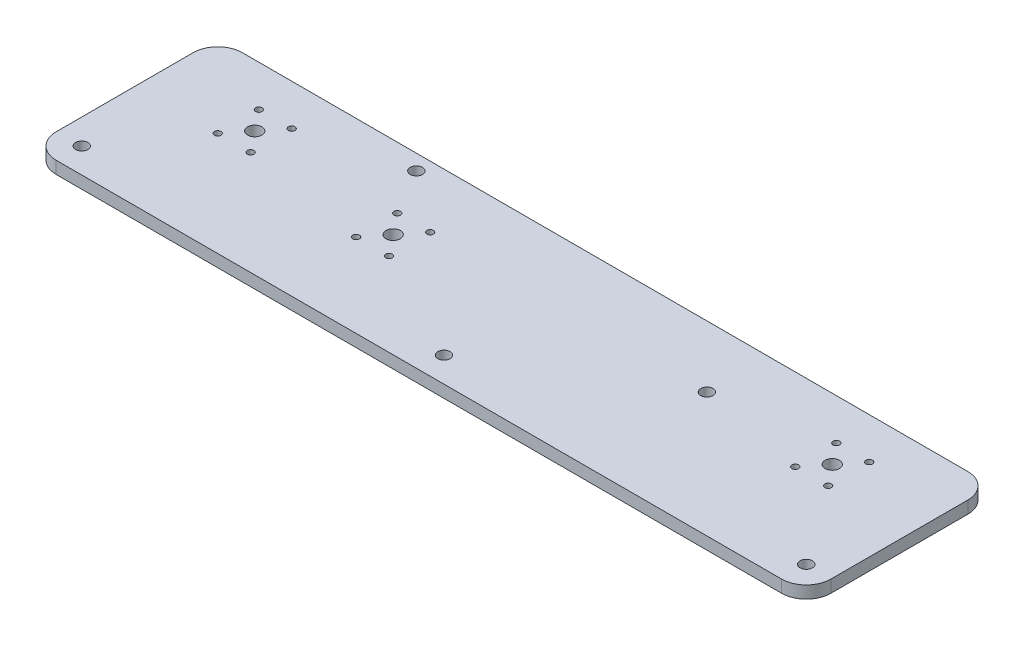
SolidWorks part; units mm, degrees
material "Policarbonato"
ref_plane "Plano frontal" through (0, 0, 0) normal (0, 0, 1) x (1, 0, 0)
ref_plane "Plano superior" through (0, 0, 0) normal (0, 1, 0) x (1, 0, 0)
ref_plane "Plano direito" through (0, 0, 0) normal (1, 0, 0) x (0, 0, -1)
sketch "Esboço1" plane through (0, 0, 0) normal (0, 1, 0) x (1, 0, 0)
  line L2 (-62.7345, -14) -> (-62.7345, 14) construction
  line L6 (188.965, -38.6487) -> (188.965, 28)
  line L7 (176.965, 40) -> (-176.0908, 40)
  line L8 (-188.0908, 28) -> (-188.0908, -38.6487)
  line L13 (-54.7345, -10) -> (-70.7345, -10) construction
  line L14 (-54.7345, -10) -> (-54.7345, 10) construction
  line L15 (-148.0908, 0) -> (-132.0908, 0) construction
  line L16 (-148.0908, 0) -> (-148.0908, 20) construction
  line L17 (-148.0908, 20) -> (-132.0908, 20) construction
  line L18 (-132.0908, 0) -> (-132.0908, 20) construction
  line L19 (-176.0908, -50.6487) -> (176.965, -50.6487)
  line L20 (-148.0908, 0) -> (-132.0908, 20) construction
  line L21 (-148.0908, 20) -> (-132.0908, 0) construction
  line L26 (-54.7345, 10) -> (-70.7345, 10) construction
  line L32 (-152.0908, 24) -> (-128.0908, -4) construction
  line L33 (-70.7345, -10) -> (-70.7345, 10) construction
  line L38 (-54.7345, -10) -> (-70.7345, 10) construction
  line L39 (-54.7345, 10) -> (-70.7345, -10) construction
  line L45 (148.965, 0) -> (132.965, 0) construction
  line L46 (148.965, 0) -> (148.965, 20) construction
  line L47 (148.965, 20) -> (132.965, 20) construction
  line L48 (132.965, 0) -> (132.965, 20) construction
  line L49 (148.965, 0) -> (132.965, 20) construction
  line L50 (148.965, 20) -> (132.965, 0) construction
  arc A0 (176.965, -50.6487) -> (188.965, -38.6487) centre (176.965, -38.6487) ccw
  arc A1 (188.965, 28) -> (176.965, 40) centre (176.965, 28) ccw
  arc A2 (-188.0908, 28) -> (-176.0908, 40) centre (-176.0908, 28) cw
  arc A3 (-188.0908, -38.6487) -> (-176.0908, -50.6487) centre (-176.0908, -38.6487) ccw
  circle A7 centre (-54.7345, -10) radius 1.6
  circle A8 centre (176.7481, -38.4318) radius 3
  circle A9 centre (0.4371, -38.4318) radius 3
  circle A10 centre (79.965, 10) radius 3
  circle A11 centre (-140.0908, 10) radius 3.5
  circle A13 centre (-148.0908, 0) radius 1.6
  circle A14 centre (-132.0908, 0) radius 1.6
  circle A15 centre (-132.0908, 20) radius 1.6
  circle A16 centre (-148.0908, 20) radius 1.6
  circle A22 centre (-83.9303, 32.5) radius 7.5 construction
  circle A24 centre (-83.9303, 32.5) radius 3
  circle A25 centre (-175.8739, -38.4318) radius 3
  circle A26 centre (-54.7345, 10) radius 1.6
  circle A27 centre (-70.7345, 10) radius 1.6
  circle A28 centre (-70.7345, -10) radius 1.6
  circle A29 centre (-62.7345, 0) radius 3.5
  circle A30 centre (132.965, 0) radius 1.6
  circle A31 centre (148.965, 0) radius 1.6
  circle A32 centre (148.965, 20) radius 1.6
  circle A33 centre (132.965, 20) radius 1.6
  circle A34 centre (140.965, 10) radius 3.5
  point P6 (-62.7345, 0)
  point P33 (0.4371, 40)
  point P39 (140.965, 10)
  dimension "D2" = 377.0558
  dimension "D4" = 7
  dimension "D6" = 12.2169
  dimension "D8" = 125.3563
  dimension "D10" = 48
  dimension "D12" = 16
  dimension "D15" = 20
  dimension "D17" = 6
  dimension "D1" = 12
  dimension "D7" = 16
  dimension "D9" = 30
  dimension "D11" = 20
  dimension "D16" = 3.2
  dimension "D20" = 48
  dimension "D25" = 56.1605
  dimension "D26" = 3.2
  dimension "D27" = 7
  dimension "D28" = 15
  dimension "D29" = 30
  dimension "D13" = 3.2
  dimension "D14" = 7
  dimension "D30" = 109
  dimension "D3" = 90.6487
  dimension "D5" = 12.2169
  dimension "D18" = 12.2169
  dimension "D19" = 50.6487
  dimension "D21" = 30
  dimension "D22" = 16
  dimension "D23" = 20
  dimension "D24" = 7.5
extrude "Ressalto-extrusão1" add sketch "Esboço1" against normal blind 6
